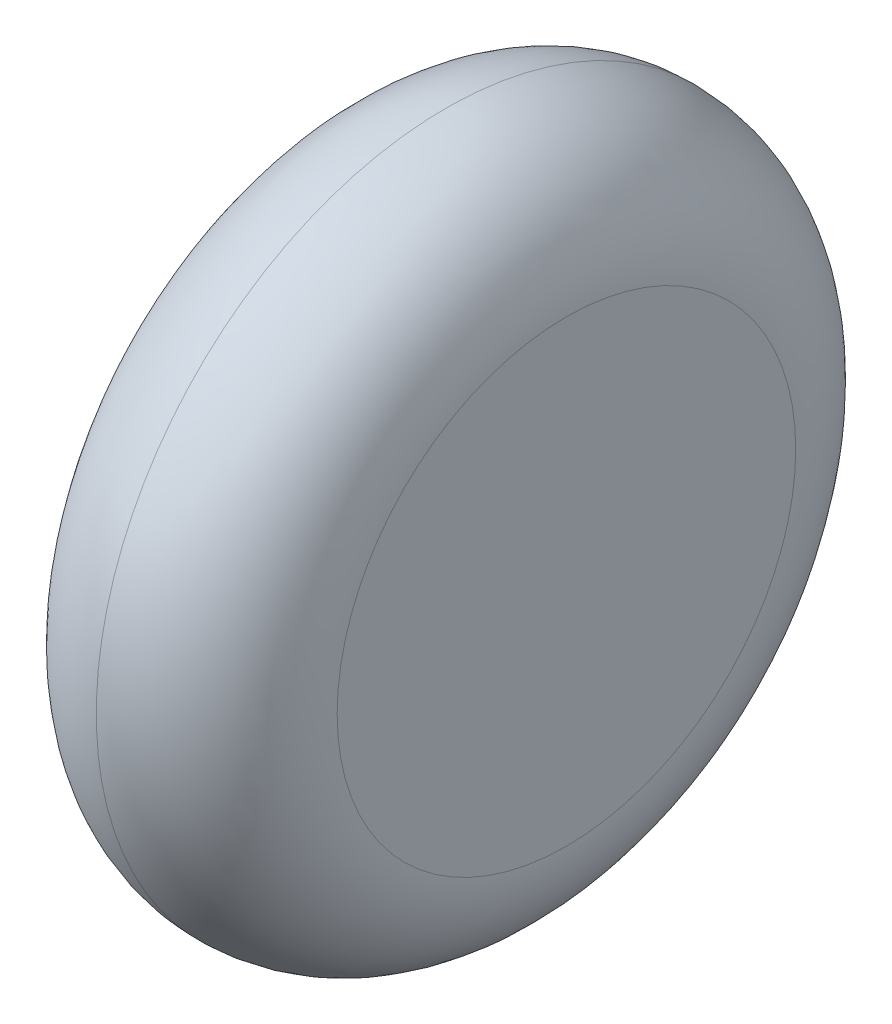
SolidWorks part; units mm, degrees
ref_plane "Front Plane" through (0, 0, 0) normal (0, 0, 1) x (1, 0, 0)
ref_plane "Top Plane" through (0, 0, 0) normal (0, 1, 0) x (1, 0, 0)
ref_plane "Right Plane" through (0, 0, 0) normal (1, 0, 0) x (0, 0, -1)
sketch "Sketch1" plane through (0, 0, 0) normal (1, 0, 0) x (0, 0, -1)
  circle A0 centre (0, 0) radius 497.84
  dimension "D1" = 995.68
extrude "Boss-Extrude1" add sketch "Sketch1" along normal mid plane 342.9
fillet "Fillet1" radius 171.45 2 edges at (-171.45, 0, -497.84) (171.45, 0, -497.84)
